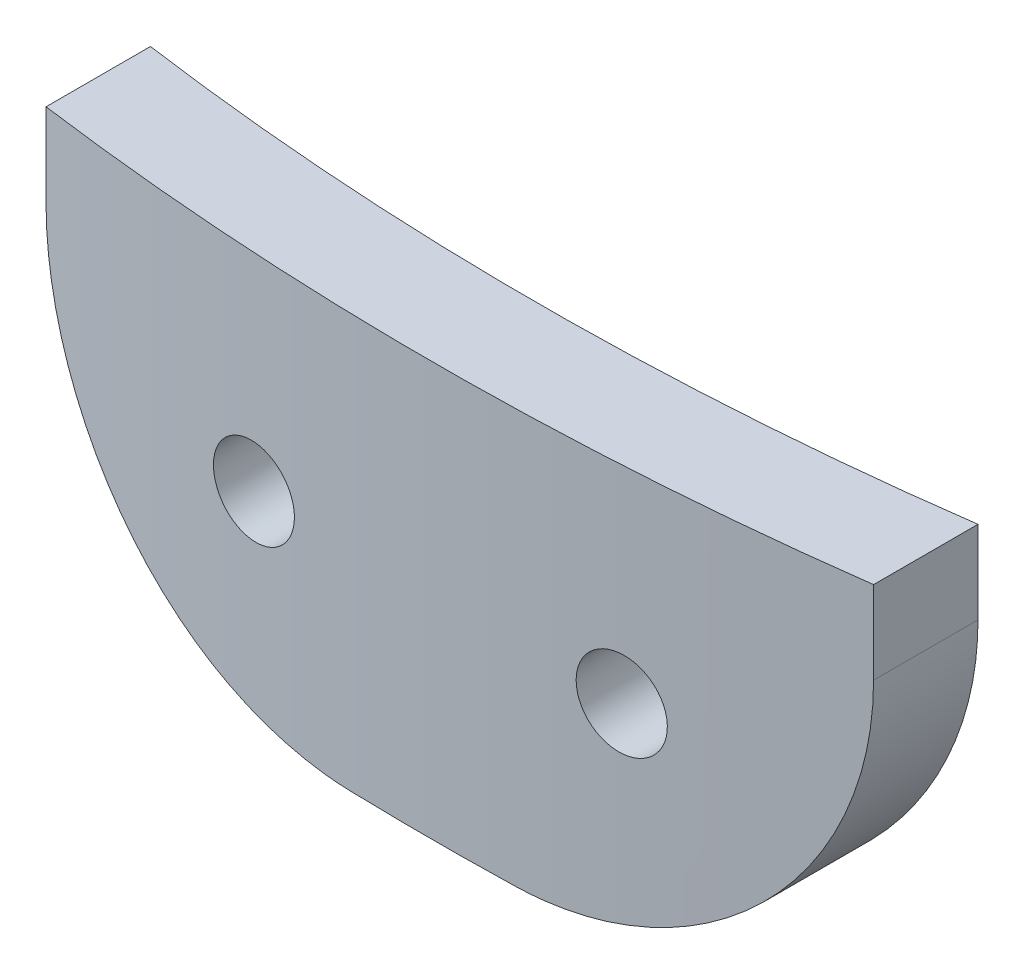
SolidWorks part; units mm, degrees
material "6061 Alloy"
ref_plane "Front Plane" through (0, 0, 0) normal (0, 0, 1) x (1, 0, 0)
ref_plane "Top Plane" through (0, 0, 0) normal (0, 1, 0) x (1, 0, 0)
ref_plane "Right Plane" through (0, 0, 0) normal (1, 0, 0) x (0, 0, -1)
sketch "Sketch1" plane through (0, 0, 0) normal (0, 1, 0) x (1, 0, 0)
  line L0 (-12.7, -91.1949) -> (-12.7, -94.3995)
  line L1 (12.7, -91.1949) -> (12.7, -94.3995)
  circle A0 centre (0, 0) radius 92.075
  circle A1 centre (0, 0) radius 95.25
  dimension "D1" = 184.15
  dimension "D3" = 12.7
  dimension "D4" = 12.7
  dimension "D2" = 3.175
extrude "Boss-Extrude1" add sketch "Sketch1" along normal blind 12.7 contours L0 A1 L1 A0 region at (0, 0, 93.3739)
sketch "Sketch2" plane through (0, 0, 0) normal (0, 0, 1) x (1, 0, 0)
  line L0 (0, 12.7) -> (0, 0) construction
  line L4 (-12.7, 0) -> (12.7, 0)
  line L5 (12.7, 0) -> (12.7, 12.7)
  line L6 (12.7, 12.7) -> (-12.7, 12.7)
  line L7 (-12.7, 12.7) -> (-12.7, 0)
  line L8 (-12.7, 0) -> (12.7, 0)
  line L9 (12.7, 0) -> (12.7, 12.7)
  line L10 (12.7, 12.7) -> (-12.7, 12.7)
  line L11 (-12.7, 12.7) -> (-12.7, 0)
  circle A0 centre (-5.6444, 6.35) radius 1.3208
  dimension "D3" = 12.7
  dimension "D6" = 2.6416
  dimension "D2" = 6.35
  dimension "D5" = 5.6444
extrude "Cut-Extrude1" cut sketch "Sketch2" along normal up to surface (95.1518 mm away) contours A0 up to face at (0, 6.35, 94.8248)
mirror "Mirror1" about plane through (0, 0, 0) normal (1, 0, 0) of "Cut-Extrude1"
sketch "Sketch3" plane through (0, 0, 0) normal (0, 0, 1) x (1, 0, 0)
  line L0 (-12.7, 12.7) -> (-12.7, 0)
  line L1 (-12.7, 0) -> (12.7, 0)
  line L2 (12.7, 0) -> (12.7, 12.7)
  line L4 (-12.7, 0) -> (12.7, 0)
  line L5 (12.7, 0) -> (12.7, 12.7)
  line L6 (12.7, 12.7) -> (-12.7, 12.7)
  line L7 (-12.7, 12.7) -> (-12.7, 0)
  line L8 (-2.54, 0) -> (2.54, 0)
  line L9 (12.7, 10.16) -> (12.7, 12.7)
  line L10 (12.7, 12.7) -> (-12.7, 12.7)
  line L11 (-12.7, 12.7) -> (-12.7, 10.16)
  arc A0 (2.54, 0) -> (12.7, 10.16) centre (2.54, 10.16) ccw
  arc A1 (-2.54, 0) -> (-12.7, 10.16) centre (-2.54, 10.16) cw
  dimension "D2" = 10.16
  dimension "D1" = 0
extrude "Cut-Extrude2" cut sketch "Sketch3" along normal up to surface (94.3995 mm away) contours L1 A1 L0 | A0 L1 L2 region at (-10.4306, 2.2694, 0) region at (10.4306, 2.2694, 0) up to face at (6.9298, 6.6537, 94.9976)
equation "\"Middle Coupler Inner Daimeter\"= 6.75in"
equation "\"Middle Coupler  Wall Thickness\" = 0.25in"
equation "\"Middle Coupler Bottom Thickness\"= 0.2in"
equation "\"Bearing Rail Offset\"= 0.45in"
equation "\"3-56 UNF Tap\"= 0.089in"
equation "\"3-56 UNF Clearance\"= 0.104in"
equation "\"Ball Bearing Distance\"= 0.03in"
equation "\"TCA Outer Diameter\" = 8.625in"
equation "\"D1@Sketch1\"=\"Middle Coupler Inner Daimeter\"+0.5"
equation "\"D2@Sketch1\"=1/8"
equation "\"D3@Sketch1\"=0.5"
equation "\"D4@Sketch1\"=\"D3@Sketch1\""
equation "\"D2@Sketch2\"=\"D3@Sketch2\"/2"
equation "\"D6@Sketch2\"=\"3-56 UNF Clearance\""
equation "\"D5@Sketch2\"=\"D4@Sketch2\"/4.5"
